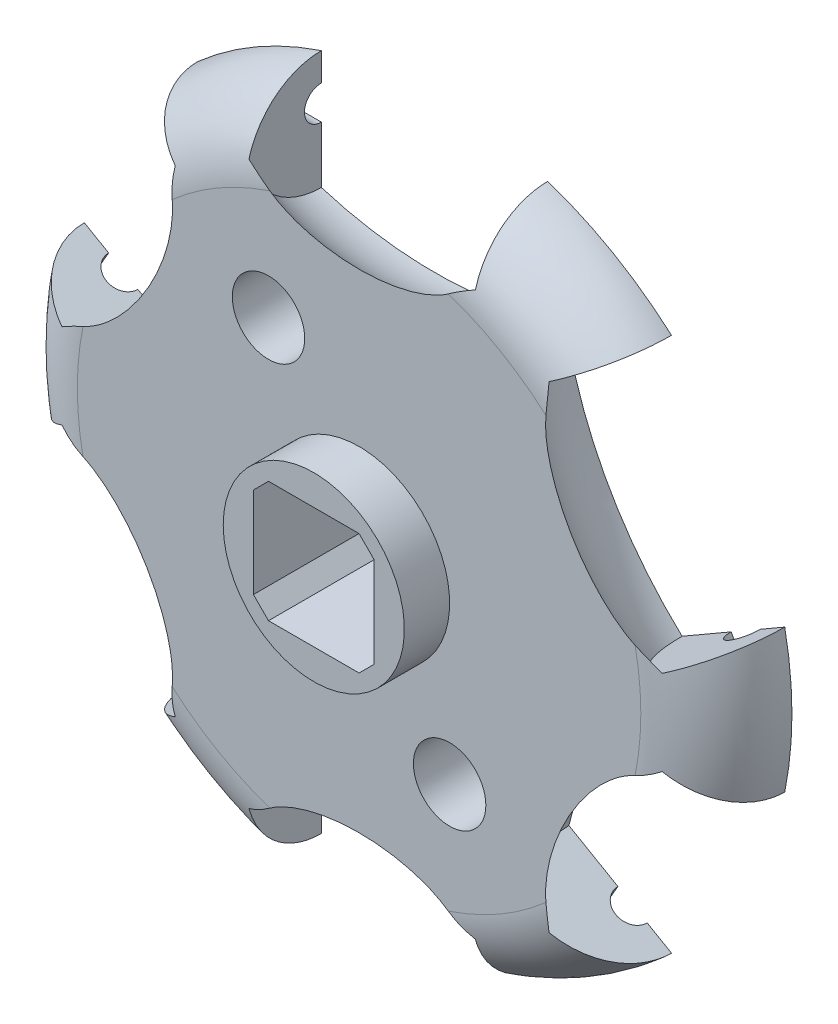
SolidWorks part; units mm, degrees
ref_plane "Front Plane" through (0, 0, 0) normal (0, 0, 1) x (1, 0, 0)
ref_plane "Top Plane" through (0, 0, 0) normal (0, 1, 0) x (1, 0, 0)
ref_plane "Right Plane" through (0, 0, 0) normal (1, 0, 0) x (0, 0, -1)
sketch "Sketch1" plane through (0, 0, 0) normal (0, 0, 1) x (1, 0, 0)
  circle A0 centre (0, 0) radius 18.796
  dimension "D1" = 37.592
extrude "Boss-Extrude1" add sketch "Sketch1" along normal blind 3.9688
fillet "Fillet1" radius 3.9789 1 edges at (18.796, 0, 3.9688)
sketch "Sketch2" plane through (0, 0, 3.9688) normal (0, 0, 1) x (1, 0, 0)
  line L0 (0, 0) -> (-9.398, 16.2778) construction
  line L1 (0, 0) -> (0, 7.1566) construction
  line L3 (-3.175, -3.175) -> (3.175, -3.175)
  line L4 (-3.175, -3.175) -> (-3.175, 3.175)
  line L5 (-3.175, 3.175) -> (3.175, 3.175)
  line L6 (3.175, -3.175) -> (3.175, 3.175)
  line L7 (-3.175, -3.175) -> (3.175, 3.175) construction
  line L8 (-3.175, 3.175) -> (3.175, -3.175) construction
  circle A0 centre (-4.7625, 8.2489) radius 1.905
  circle A1 centre (4.7625, -8.2489) radius 1.905
  circle A4 centre (0, 0) radius 18.796 construction
  point P9 (0, 0)
  dimension "D2" = 3.81
  dimension "D4" = 6.35
  dimension "D1" = 9.525
  dimension "D5" = 30
  dimension "D6" = 6.35
  dimension "D3" = 2
extrude "Cut-Extrude1" cut sketch "Sketch2" against normal through all
sketch "Sketch5" plane through (0, 0, 0) normal (0, 0, 1) x (1, 0, 0)
  line L0 (-5.9531, 15.4623) -> (5.9531, 15.4623)
  line L1 (5.9531, 15.4623) -> (5.9531, 19.3288)
  line L2 (-5.9531, 15.4623) -> (-5.9531, 19.3288)
  line L3 (-5.9531, 15.4623) -> (-8.5086, 15.4623) construction
  arc A0 (-5.9531, 19.3288) -> (5.9531, 19.3288) centre (0, 0) cw
  circle A1 centre (0, 0) radius 18.796 construction
  point P5 (0, 15.4623)
  point P9 (0, 20.2248)
  dimension "D1" = 11.9062
  dimension "D2" = 15.4623
  dimension "D3" = 9.525
revolve "Cut-Revolve1" cut sketch "Sketch5" angle 360 about L3
sketch "Sketch6" plane through (0, 0, 0) normal (1, 0, 0) x (0, 0, -1)
  line L0 (0, -18.796) -> (0, 17.8283) construction
  circle A0 centre (0, 15.4623) radius 0.889
  arc A1 (-3.807, 14.7866) -> (0, 11.5957) centre (0, 15.4623) ccw construction
  dimension "D1" = 1.778
extrude "Cut-Extrude2" cut sketch "Sketch6" against normal mid plane 15.875
pattern_circular "CirPattern1" count 6 over 360 about axis through (0, 0, 3.9688) along (0, 0, 1) of "Cut-Revolve1", "Cut-Extrude2"
sketch "Sketch7" plane through (0, 0, 3.9688) normal (0, 0, 1) x (1, 0, 0)
  line L5 (3.175, -3.175) -> (3.175, 3.175)
  line L6 (-3.175, -3.175) -> (3.175, -3.175)
  line L7 (-3.175, 3.175) -> (-3.175, -3.175)
  line L8 (3.175, 3.175) -> (-3.175, 3.175)
  line L9 (3.175, -3.175) -> (3.175, 3.175)
  line L10 (-3.175, -3.175) -> (3.175, -3.175)
  line L11 (-3.175, 3.175) -> (-3.175, -3.175)
  line L12 (3.175, 3.175) -> (-3.175, 3.175)
  circle A0 centre (0, 0) radius 4.7625
  dimension "D2" = 9.525
  dimension "D1" = 0
extrude "Boss-Extrude2" add sketch "Sketch7" along normal blind 2.3813
chamfer "Chamfer1" distance 0.7937 angle 45 4 edges at (3.175, -3.175, 3.175) (-3.175, -3.175, 3.175) (-3.175, 3.175, 3.175) (3.175, 3.175, 3.175)
